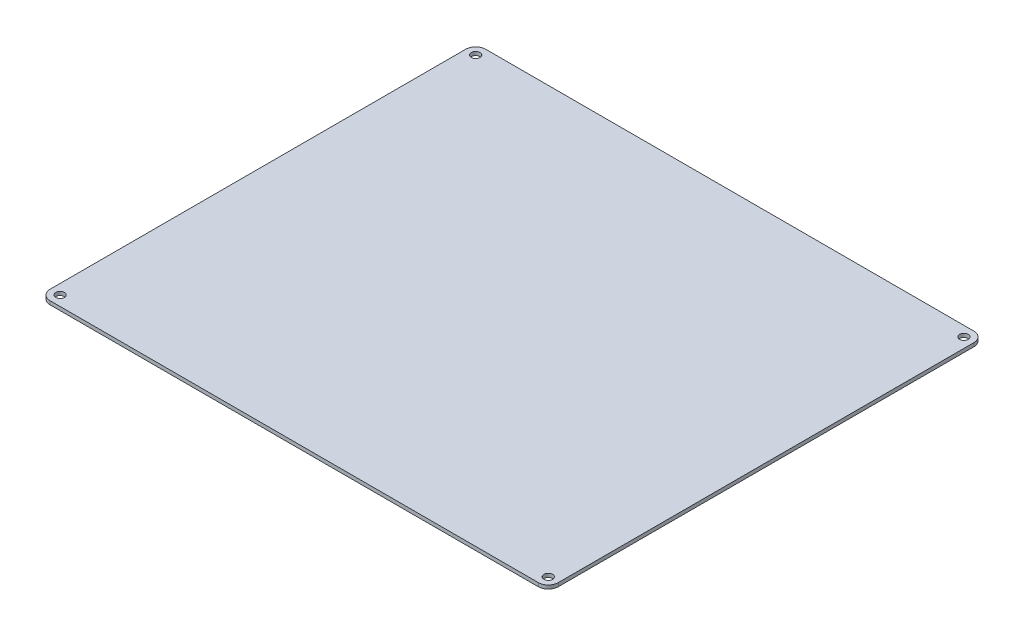
SolidWorks part; units mm, degrees
ref_plane "Front Plane" through (0, 0, 0) normal (0, 0, 1) x (1, 0, 0)
ref_plane "Top Plane" through (0, 0, 0) normal (0, 1, 0) x (1, 0, 0)
ref_plane "Right Plane" through (0, 0, 0) normal (1, 0, 0) x (0, 0, -1)
sketch "Sketch1" plane through (0, 0, 0) normal (0, 1, 0) x (1, 0, 0)
  line L0 (70, 0) -> (70, -120) construction
  line L1 (0, 0) -> (140, 0)
  line L2 (0, 0) -> (0, -120)
  line L3 (0, -120) -> (140, -120)
  line L4 (140, 0) -> (140, -120)
  line L5 (2.75, -2.75) -> (0, -2.75) construction
  line L6 (0, -60) -> (140, -60) construction
  line L8 (2.75, 0) -> (2.75, -2.75) construction
  circle A0 centre (2.75, -2.75) radius 1.2
  circle A1 centre (137.25, -2.75) radius 1.2
  circle A2 centre (137.25, -117.25) radius 1.2
  circle A3 centre (2.75, -117.25) radius 1.2
  dimension "D3" = 2.4
  dimension "D4" = 2.75
  dimension "D1" = 140
  dimension "D2" = 120
extrude "Boss-Extrude1" add sketch "Sketch1" along normal blind 1
fillet "Fillet1" radius 2.75 4 edges at (0, 0.5, 0) (140, 0.5, 0) (140, 0.5, 120) (0, 0.5, 120)
